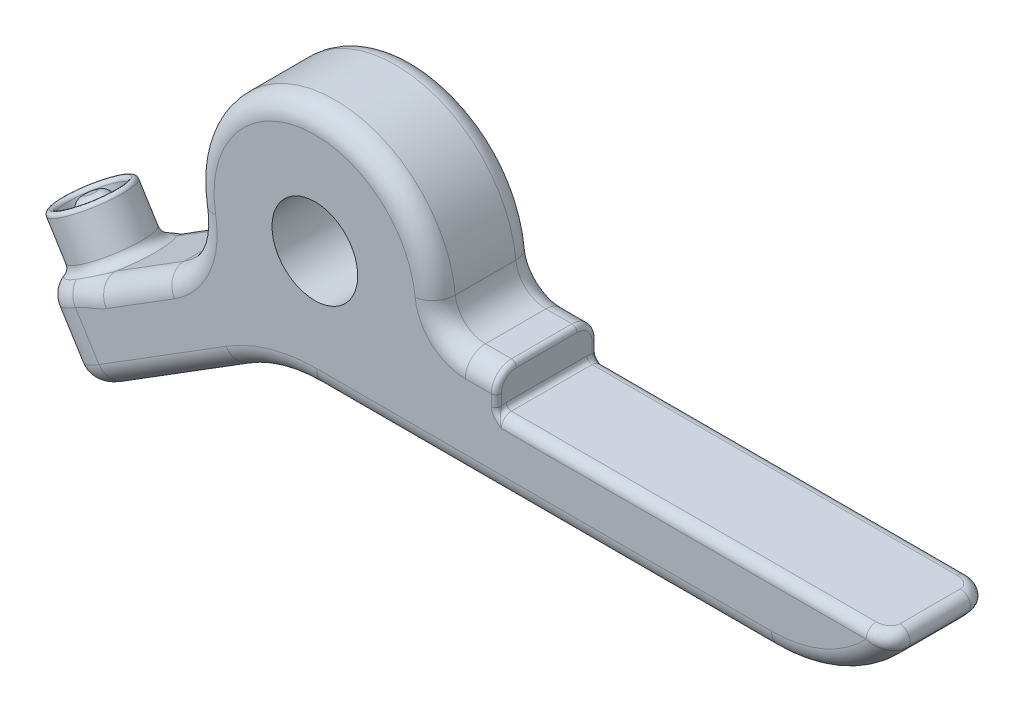
SolidWorks part; units mm, degrees
ref_plane "Piano frontale" through (0, 0, 0) normal (0, 0, 1) x (1, 0, 0)
ref_plane "Piano superiore" through (0, 0, 0) normal (0, 1, 0) x (1, 0, 0)
ref_plane "Piano destro" through (0, 0, 0) normal (1, 0, 0) x (0, 0, -1)
sketch "Schizzo1" plane through (0, 0, 0) normal (0, 0, 1) x (1, 0, 0)
  line L0 (0, 24.3243) -> (0, -21.4525) construction
  line L1 (-100.7155, 0) -> (52.4681, 0) construction
  line L2 (-10.1766, -6.359) -> (-28.8336, -18.0173)
  line L3 (11.9059, -1.5) -> (18, -1.5)
  line L4 (18, -1.5) -> (18, -5)
  line L5 (18, -5) -> (58, -5)
  line L6 (58, -5) -> (58, -12)
  line L7 (58, -12) -> (0, -12)
  line L19 (-28.8336, -18.0173) -> (-24.5943, -24.8016)
  line L20 (-3.3458, -11.5241) -> (-24.5943, -24.8016)
  line L22 (4.2394, -6.7844) -> (-24.5943, -24.8016) construction
  line L23 (0, 0) -> (-28.8336, -18.0173) construction
  arc A0 (11.9059, -1.5) -> (-0.5819, 11.9859) centre (0, 0) ccw
  circle A1 centre (0, 0) radius 4.25
  arc A5 (-0.5819, 11.9859) -> (-10.1766, -6.359) centre (0, 0) ccw
  arc A18 (-3.3458, -11.5241) -> (0, -12) centre (0, 0) ccw
  point P17 (-47, -5.1624)
  point P18 (-24.5358, 39.507)
  point P20 (0.3611, 10.8664)
  point P23 (-48, -1.1755)
  point P24 (-40.5832, 5)
  point P25 (-26.2582, 46.6028)
  point P26 (-47, -5.1624)
  point P27 (3.0168, 10.9194)
  point P28 (-32.0472, 45.1549)
  point P29 (-24.7058, 39.1689)
  point P30 (0.0026, 10.7451)
  point P32 (-0.136, 9.3145)
  dimension "D1" = 8.5
  dimension "D2" = 24
  dimension "D4" = 34
  dimension "D5" = 8
  dimension "D3" = 32
  dimension "D6" = 18
  dimension "D7" = 58
  dimension "D8" = 5
  dimension "1.5" = 1.5
extrude "Estrusione-Estrusione1" add sketch "Schizzo1" along normal blind 17
sketch "Schizzo2" plane through (0, 0, 0) normal (0, 1, 0) x (1, 0, 0)
  line L0 (0, 9.2219) -> (0, -29.9222) construction
  line L10 (12, 0) -> (-12, 0) construction
  line L11 (-100, 8) -> (100, 8)
  line L12 (-100, 8) -> (-100, -7)
  line L13 (-100, -7) -> (100, -7)
  line L14 (100, 8) -> (100, -7)
  dimension "D1" = 7
  dimension "D2" = 200
  dimension "D3" = 15
  dimension "D4" = 100
extrude "Taglio-Estrusione3" cut sketch "Schizzo2" against normal through all both and the other way through all
sketch "Schizzo3" plane through (0, 0, 0) normal (-0.5299, 0.848, 0) x (0.848, 0.5299, 0)
  line L0 (0, 0) -> (0, -34.7498) construction
  circle A0 centre (-29, -12) radius 1.6
  dimension "D3" = 3.2
  dimension "D1" = 29
  dimension "D2" = 12
extrude "Estrusione-Estrusione2" add sketch "Schizzo3" along normal blind 5
sketch "Schizzo4" plane through (0, 0, 7) normal (0, 0, -1) x (-1, 0, 0)
  circle A0 centre (0, 0) radius 6.25
  dimension "D1" = 12.5
extrude "Taglio-Estrusione4" cut sketch "Schizzo4" against normal blind 0.5
draft "Sformo1" type of draft neutral plane draft angle 1 faces to draft 1 face at (-28.5999, -11.9753, 12) neutral plane through (-10.1766, -6.359, 17) neutral plane normal (-0.5299, 0.848, 0) parameters "D1"=1
sketch "Schizzo5" plane through (0, 0, 0) normal (-0.5299, 0.848, 0) x (0.848, 0.5299, 0)
  circle A0 centre (-29, -12) radius 3.5
  circle A1 centre (-29, -12) radius 2.75
  dimension "D1" = 5.5
  dimension "D2" = 0.75
extrude "Estrusione-Estrusione3" add sketch "Schizzo5" along normal blind 5
fillet "Raccordo28" radius 15 4 edges at (-1.6897, -11.8804, 17) (0, -12, 12) (-3.3458, -11.5241, 12) (-1.6897, -11.8804, 7)
fillet "Raccordo29" radius 7 1 edges at (-10.1766, -6.359, 12)
fillet "Raccordo25" radius 15 1 edges at (58, -12, 12)
fillet "Raccordo15" radius 3 1 edges at (11.9059, -1.5, 12)
fillet "Raccordo30" radius 5 2 edges at (-26.714, -21.4094, 7) (-26.714, -21.4094, 17)
fillet "Raccordo35" radius 1 1 edges at (-21.6252, -13.5129, 12)
fillet "Raccordo23" radius 2 12 edges at (16.4624, -1.5, 17) (12.9124, -0.7249, 17) (16.4624, -1.5, 7) (12.9124, -0.7249, 7) (-1.6826, 11.8814, 17) (-1.6826, 11.8814, 7) (-19.7865, -12.3639, 17) (-12.2847, -6.2497, 17) (-19.7865, -12.3639, 7) (-12.2847, -6.2497, 7) (-27.5917, -17.2412, 15.5355) (-27.5917, -17.2412, 8.4645)
fillet "Raccordo27" radius 2 10 edges at (52.5571, -10.1339, 7) (52.5571, -10.1339, 17) (-14.0545, -18.2157, 7) (22.7526, -12, 7) (22.7526, -12, 17) (-14.0545, -18.2157, 17) (-23.3523, -24.0256, 8.4645) (-23.3523, -24.0256, 15.5355) (-3.9408, -12.5811, 7) (-3.9408, -12.5811, 17)
fillet "Raccordo32" radius 1 5 edges at (57.2629, -5, 16.4458) (57.1535, -5, 7.4725) (58, -5, 12) (36.7792, -5, 17) (36.7792, -5, 7)
fillet "Raccordo33" radius 0.5 8 edges at (18, -5, 12) (18, -2.0858, 16.4142) (18, -1.5, 12) (18, -2.0858, 7.5858) (18, -4.75, 7) (18, -4.75, 17) (18, -5.2929, 16.7071) (18, -5.2929, 7.2929)
fillet "Raccordo34" radius 1 2 edges at (-23.2365, -14.5198, 12) (-28.5259, -11.929, 12)
fillet "Raccordo36" radius 0.375 2 edges at (-29.5751, -12.5847, 12) (-30.2112, -12.9821, 12)
fillet "Raccordo37" radius 0.2 1 edges at (-6.25, 0, 7)
